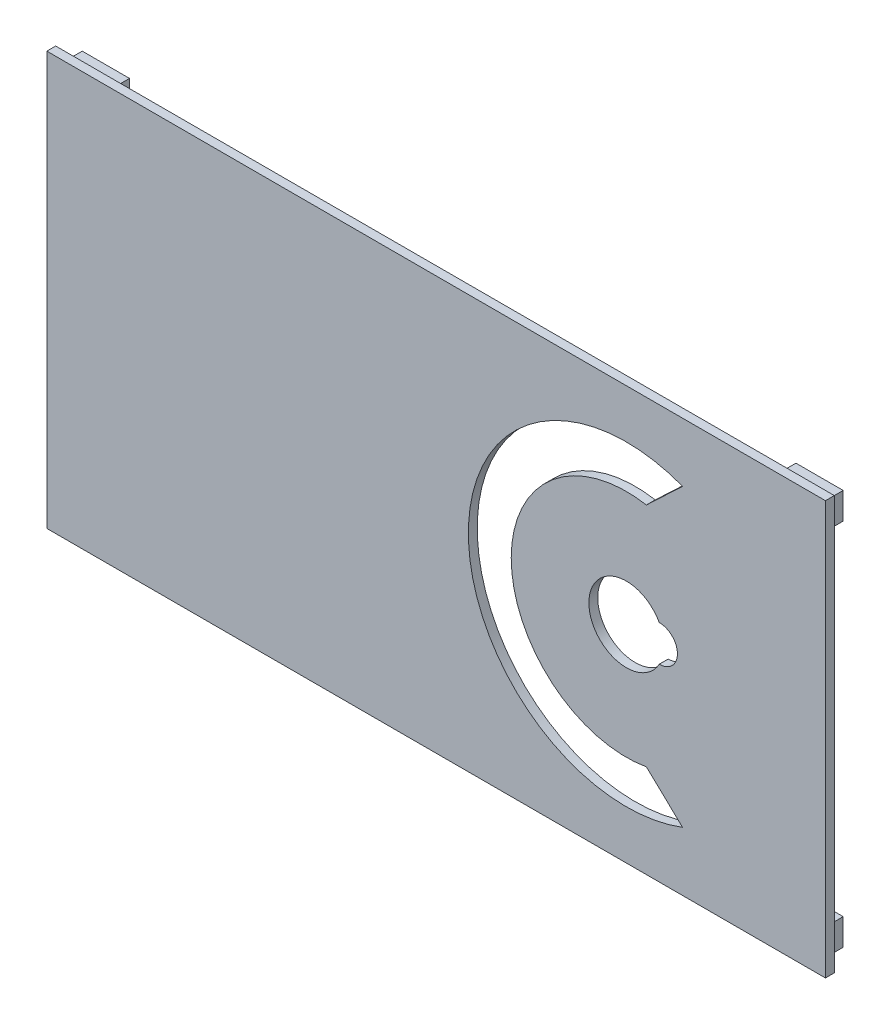
SolidWorks part; units mm, degrees
ref_plane "Front Plane" through (0, 0, 0) normal (0, 0, 1) x (1, 0, 0)
ref_plane "Top Plane" through (0, 0, 0) normal (0, 1, 0) x (1, 0, 0)
ref_plane "Right Plane" through (0, 0, 0) normal (1, 0, 0) x (0, 0, -1)
sketch "Sketch1" plane through (0, 0, 0) normal (0, 0, 1) x (1, 0, 0)
  line L0 (121.1, -9.75) -> (-10.75, -9.75)
  line L1 (119.6, -8.25) -> (-9.25, -8.25)
  line L2 (119.6, -8.25) -> (119.6, 58.75)
  line L3 (119.6, 58.75) -> (-9.25, 58.75)
  line L4 (-9.25, -8.25) -> (-9.25, 58.75)
  line L5 (-10.75, -9.75) -> (-10.75, 60.25)
  line L6 (121.1, 60.25) -> (-10.75, 60.25)
  line L7 (121.1, -9.75) -> (121.1, 60.25)
  dimension "D1" = 1.5
extrude "Boss-Extrude1" add sketch "Sketch1" along normal blind 1.5 contours L7 L6 L5 L0
sketch "Sketch2" plane through (0, 0, 1.5) normal (0, 0, 1) x (1, 0, 0)
  line L5 (92.9571, 22.2) -> (92.9875, 22.2)
  line L6 (92.9875, 28.3) -> (92.9571, 28.3)
  line L7 (92.9571, 22.2) -> (92.9875, 22.2)
  line L8 (92.9875, 28.3) -> (92.9571, 28.3)
  arc A10 (92.9875, 22.2) -> (92.9875, 28.3) centre (92.9875, 25.25) ccw
  arc A11 (92.9571, 28.3) -> (92.9571, 22.2) centre (87.3875, 25.25) ccw
  arc A12 (92.9875, 22.2) -> (92.9875, 28.3) centre (92.9875, 25.25) ccw
  arc A13 (92.9571, 28.3) -> (92.9571, 22.2) centre (87.3875, 25.25) ccw
  dimension "D1" = 0.25
extrude "Cut-Extrude1" cut sketch "Sketch2" against normal up to next
ref_plane "Plane2" through (0, 25.25, 0) normal (0, 1, 0) x (1, 0, 0)
ref_plane "Plane1" through (55.175, 0, 0) normal (1, 0, 0) x (0, 0, -1)
sketch "Sketch3" plane through (121.1, 0, 0) normal (1, 0, 0) x (0, 0, -1)
  line L0 (0, -9.75) -> (0, 60.25) construction
  line L1 (-1.5, 60.25) -> (6, 60.25)
  line L2 (-1.5, 60.25) -> (-1.5, 61.75)
  line L3 (-1.5, 61.75) -> (6, 61.75)
  line L4 (6, 60.25) -> (6, 61.75)
  line L5 (6, 60.25) -> (4.5, 58.75)
  line L7 (4.5, 58.75) -> (4.5, 60.25)
  dimension "D1" = 1.5
  dimension "D2" = 6
  dimension "D3" = 45
sketch "Sketch4" plane through (0, 0, 0) normal (0, 0, -1) x (-1, 0, 0)
  line L0 (-118.1, 57.25) -> (-118.1, 55.75)
  line L1 (-119.6, 58.75) -> (-111.6, 58.75)
  line L2 (-119.6, 58.75) -> (-119.6, 54.25)
  line L3 (-119.6, 54.25) -> (-111.6, 54.25)
  line L4 (-111.6, 58.75) -> (-111.6, 54.25)
  line L5 (-119.6, 58.75) -> (-119.6, 60.25) construction
  line L6 (-118.1, 55.75) -> (-113.1, 55.75)
  line L7 (-121.1, 60.25) -> (10.75, 60.25) construction
  line L8 (-113.1, 57.25) -> (-113.1, 55.75)
  line L9 (-118.1, 57.25) -> (-113.1, 57.25)
  line L10 (-119.6, 58.75) -> (-121.1, 58.75) construction
  line L11 (-121.1, -9.75) -> (-121.1, 60.25) construction
  dimension "D1" = 1.5
  dimension "D2" = 5
  dimension "D3" = 1.5
extrude "Boss-Extrude2" add sketch "Sketch4" along normal blind 3
mirror "Mirror1" about plane through (0, 25.25, 0) normal (0, 1, 0) of "Boss-Extrude2"
mirror "Mirror2" about plane through (55.175, 0, 0) normal (1, 0, 0) of "Mirror1", "Boss-Extrude2"
sketch "Sketch5" plane through (0, 0, 1.5) normal (0, 0, 1) x (1, 0, 0)
  line L0 (62.3875, 28.95) -> (62.3875, 21.55) construction
  line L1 (62.3875, 28.95) -> (62.3875, 21.55) construction
  line L2 (60.8875, 28.95) -> (60.8875, 21.55) construction
  line L3 (60.8875, 28.95) -> (60.8875, 21.55) construction
  line L4 (60.8875, 28.95) -> (62.3875, 28.95) construction
  line L5 (60.8875, 28.95) -> (62.3875, 28.95) construction
  line L6 (60.8875, 21.55) -> (62.3875, 21.55) construction
  line L7 (60.8875, 21.55) -> (62.3875, 21.55) construction
  line L8 (67.8875, 21.55) -> (66.3875, 21.55) construction
  line L9 (67.8875, 28.95) -> (66.3875, 28.95) construction
  line L10 (67.8875, 26.1038) -> (67.8875, 24.3962) construction
  line L11 (90.7742, 6.0464) -> (96.9081, 0.244)
  line L12 (60.8875, 21.55) -> (67.8875, 21.55) construction
  line L13 (60.8875, 21.55) -> (60.8875, 28.95) construction
  line L14 (60.8875, 28.95) -> (67.8875, 28.95) construction
  line L15 (67.8875, 21.55) -> (67.8875, 28.95) construction
  line L16 (83.6875, 51.75) -> (91.0875, 51.75) construction
  line L17 (83.6875, 51.75) -> (83.6875, 44.75) construction
  line L18 (83.6875, 44.75) -> (91.0875, 44.75) construction
  line L19 (91.0875, 51.75) -> (91.0875, 44.75) construction
  line L20 (67.8875, 21.55) -> (70.3875, 21.55)
  line L21 (70.3875, 21.55) -> (70.3875, 28.95)
  line L22 (70.3875, 28.95) -> (67.8875, 28.95)
  line L23 (67.8875, 28.95) -> (67.8875, 26.1038)
  line L24 (67.8875, 26.1038) -> (66.3875, 26.1038)
  line L25 (66.3875, 26.1038) -> (66.3875, 28.95)
  line L26 (66.3875, 28.95) -> (63.8875, 28.95)
  line L27 (63.8875, 28.95) -> (63.8875, 21.55)
  line L28 (63.8875, 21.55) -> (66.3875, 21.55)
  line L29 (66.3875, 21.55) -> (66.3875, 24.3962)
  line L30 (66.3875, 24.3962) -> (67.8875, 24.3962)
  line L31 (67.8875, 24.3962) -> (67.8875, 21.55)
  line L32 (83.6875, 51.75) -> (91.0875, 44.75) construction
  line L33 (83.6875, 44.75) -> (91.0875, 51.75) construction
  line L34 (83.6875, 5.75) -> (91.0875, 5.75) construction
  line L35 (67.8875, 28.95) -> (67.8875, 26.1038) construction
  line L36 (67.8875, 26.1038) -> (66.3875, 26.1038) construction
  line L37 (66.3875, 26.1038) -> (66.3875, 28.95) construction
  line L38 (83.6875, 5.75) -> (83.6875, -1.25) construction
  line L39 (83.6875, -1.25) -> (91.0875, -1.25) construction
  line L40 (91.0875, 5.75) -> (91.0875, -1.25) construction
  line L41 (66.3875, 21.55) -> (66.3875, 24.3962) construction
  line L42 (66.3875, 24.3962) -> (67.8875, 24.3962) construction
  line L43 (67.8875, 24.3962) -> (67.8875, 21.55) construction
  line L44 (83.6875, 5.75) -> (91.0875, -1.25) construction
  line L45 (83.6875, -1.25) -> (91.0875, 5.75) construction
  line L46 (90.7742, 44.4536) -> (96.9081, 50.256)
  arc A0 (96.9081, 50.256) -> (96.9081, 0.244) centre (87.3875, 25.25) ccw
  arc A1 (90.7742, 44.4536) -> (90.7742, 6.0464) centre (87.3875, 25.25) ccw
  point P19 (67.8875, 25.25)
  point P20 (87.3875, 48.25)
  point P25 (87.3875, 2.25)
  point P26 (87.3875, 44.75)
  point P31 (0, 0)
  point P32 (87.3875, 5.75)
  point P36 (0, 0)
  point P37 (90.7742, 44.4531)
  dimension "D1" = 0
extrude "Cut-Extrude2" cut sketch "Sketch5" against normal up to next
equation "\"D1@Boss-Extrude2\"=1.50mm+.25"
